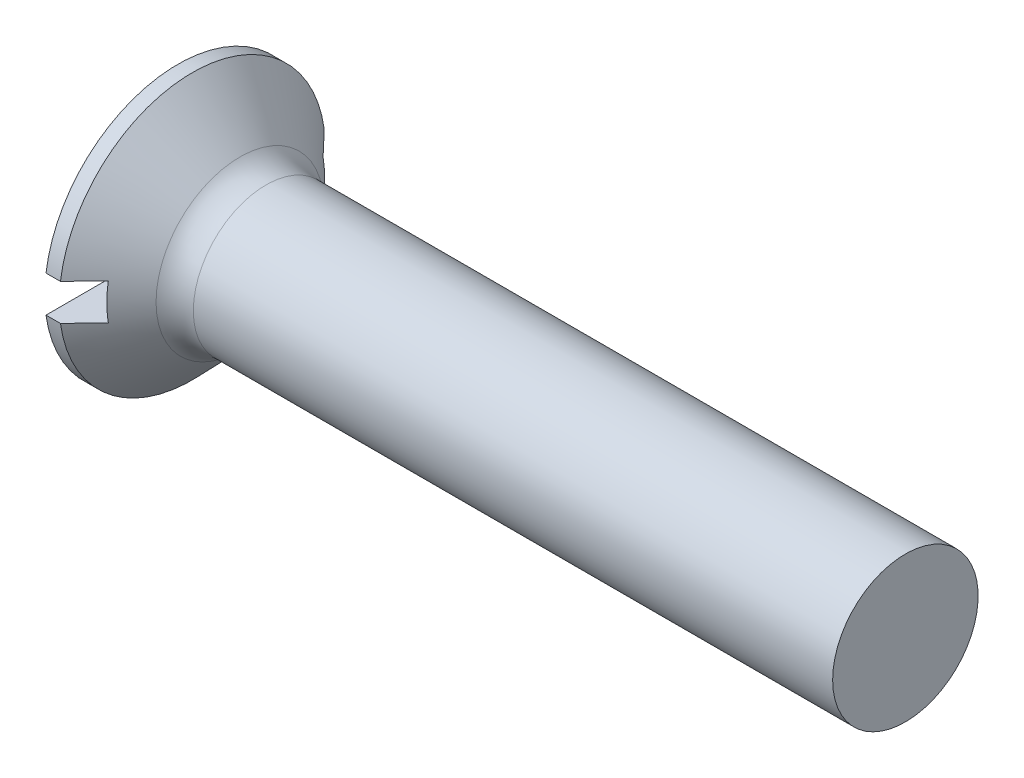
SolidWorks part; units mm, degrees
ref_plane "Front Plane" through (0, 0, 0) normal (0, 0, 1) x (1, 0, 0)
ref_plane "Top Plane" through (0, 0, 0) normal (0, 1, 0) x (1, 0, 0)
ref_plane "Right Plane" through (0, 0, 0) normal (1, 0, 0) x (0, 0, -1)
sketch "BodySke" plane through (0, 0, 0) normal (0, 0, 1) x (1, 0, 0)
  line L0 (0, 0) -> (111.3824, 0) construction
  line L1 (0, 0) -> (0, 9.15)
  line L2 (0, 9.15) -> (0.9924, 9.15)
  line L3 (0.9924, 9.15) -> (5, 5)
  line L4 (5, 5) -> (50, 5)
  line L5 (50, 5) -> (50, 0)
  line L6 (6.5, 8.824) -> (6.5, -5.8939) construction
  line L7 (0, 0) -> (50, 0)
  line L8 (12, 8.824) -> (12, -4.958) construction
  line L9 (0, -9.15) -> (0.9924, -9.15) construction
  line L10 (0.9924, -9.15) -> (5, -5) construction
  line L11 (5, -5) -> (50, -5) construction
  point P10 (50, 4.172)
  dimension "Thread_minor" = 8.344
  dimension "Length" = 50
  dimension "Head_height" = 5
  dimension "Head_dia" = 18.3
  dimension "Advance" = 1.5
revolve "BaseBody" add sketch "BodySke" angle 360 about L0
cosmetic thread "ThreadCosmetic" [suppressed] parameters "Thread_minor"=8.344
fillet "Fillet1" radius 2.5 1 edges at (5, 0, 5)
sketch "SlotSke" plane through (0, 0, 0) normal (-1, 0, 0) x (0, 0, 1)
  line L1 (-9.15, 1.25) -> (9.15, 1.25)
  line L2 (-9.15, 1.25) -> (-9.15, -1.25)
  line L3 (-9.15, -1.25) -> (9.15, -1.25)
  line L4 (9.15, 1.25) -> (9.15, -1.25)
  dimension "D1" = 18.3
  dimension "D2" = 9.15
  dimension "D3" = 1.25
extrude "Slot" cut sketch "SlotSke" against normal blind 2.6
sketch "ThdSchSke" plane through (0, 0, 0) normal (0, 0, 1) x (1, 0, 0)
  line L0 (0, 0) -> (55.1256, 0) construction
  line L1 (0, 0) -> (111.3824, 0) construction
  line L2 (49.522, 5) -> (49.522, 5.9561)
  line L3 (49.522, 5.9561) -> (50.478, 5.9561)
  line L4 (50.478, 5.9561) -> (50.478, 5)
  line L5 (50.478, 5) -> (50, 4.172)
  line L6 (50, 4.172) -> (49.522, 5)
  line L7 (5, 5) -> (50, 5) construction
  line L13 (50, 5) -> (50, 0) construction
revolve "ThreadSchematic" [suppressed] cut sketch "ThdSchSke" angle 360 about L0
pattern_linear "ThdSchPat" [suppressed] count 25 along (-1, 0, 0) of bodies 103
equation "\"Thread_minor@ThreadCosmetic\" = \"Thread_minor@BodySke\""
equation "\"D1@SlotSke\" = \"Head_dia@BodySke\""
equation "\"D2@SlotSke\" = \"D1@SlotSke\" / 2"
equation "\"D3@SlotSke\" = \"Slot_width@SlotSke\" / 2"
equation "\"Advance@ThdSchPat\" = \"Advance@BodySke\""
equation "\"D1@ThdSchPat\" =  int( \"Thread_length@BodySke\" / \"Advance@ThdSchPat\" )  "
